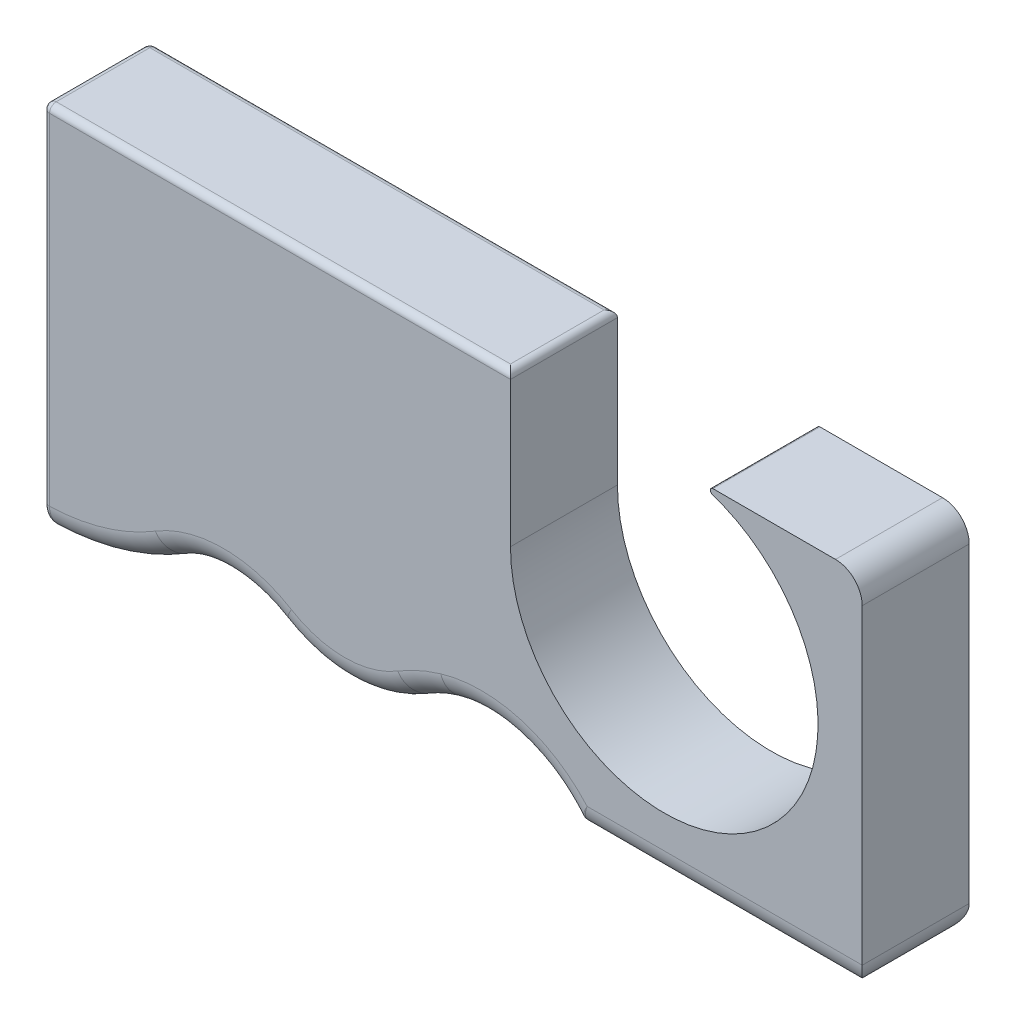
SolidWorks part; units mm, degrees
material "Pure Gold"
ref_plane "Front Plane" through (0, 0, 0) normal (0, 0, 1) x (1, 0, 0)
ref_plane "Top Plane" through (0, 0, 0) normal (0, 1, 0) x (1, 0, 0)
ref_plane "Right Plane" through (0, 0, 0) normal (1, 0, 0) x (0, 0, -1)
sketch "Sketch1" plane through (0, 0, 0) normal (0, 0, 1) x (1, 0, 0)
  line L0 (0, 0) -> (0, 177.546)
  line L1 (0, 177.546) -> (222.9415, 177.546)
  line L3 (389.137, 177.546) -> (222.9415, 177.546)
  line L4 (252.4172, 4.2874) -> (389.137, 4.2874)
  line L5 (389.137, 177.546) -> (389.137, 4.2874)
  arc A0 (0, 0) -> (60.0553, 16.8316) centre (0, 115.5548) ccw
  arc A1 (60.0553, 16.8316) -> (111.4708, 16.8316) centre (85.763, -25.4287) cw
  arc A2 (111.4708, 16.8316) -> (175.1616, 16.8316) centre (143.3162, 69.1813) ccw
  arc A3 (175.1616, 16.8316) -> (192.6023, 24.5751) centre (213.8069, -46.6965) cw
  arc A8 (192.6023, 24.5751) -> (252.4172, 4.2874) centre (208.1854, -27.8017) cw
  dimension "D1" = 177.546
extrude "Boss-Extrude1" add sketch "Sketch1" along normal blind 50.8
sketch "Sketch2" plane through (0, 0, 50.8) normal (0, 0, 1) x (1, 0, 0)
  line L0 (222.0744, 177.546) -> (222.0744, 105.5682)
  line L1 (389.137, 177.546) -> (0, 177.546) construction
  line L2 (222.0744, 177.546) -> (239.7169, 177.546)
  arc A1 (222.0744, 105.5682) -> (322.9091, 173.1035) centre (295.108, 105.5682) ccw
  arc A3 (322.9091, 173.1035) -> (239.7169, 177.546) centre (274.9764, 56.6636) ccw
  dimension "D1" = 73.0337
  dimension "D2" = 125.9198
  dimension "D3" = 222.0744
  dimension "D4" = 239.7169
  dimension "D5" = 274.9764
extrude "Cut-Extrude1" cut sketch "Sketch2" against normal through all
fillet "Fillet1" radius 2.54 1 edges at (252.4172, 4.2874, 25.4)
fillet "Fillet2" radius 12.7 15 edges at (31.1847, 4.2874, 0) (85.763, 24.0366, 0) (143.3162, 7.9063, 0) (183.6325, 21.2652, 0) (225.1456, 24.1456, 0) (31.1847, 4.2874, 50.8) (85.763, 24.0366, 50.8) (143.3162, 7.9063, 50.8) (183.6325, 21.2652, 50.8) (225.1456, 24.1456, 50.8) (389.137, 4.2874, 25.4) (321.4155, 4.2874, 0) (321.4155, 4.2874, 50.8) (252.5661, 4.5516, 0) (252.5661, 4.5516, 50.8)
fillet "Fillet8" radius 1.27 1 edges at (310.2359, 177.546, 25.4)
fillet "Fillet11" radius 12.7 1 edges at (389.137, 177.546, 25.4)
fillet "Fillet12" radius 3.175 4 edges at (111.0372, 177.546, 0) (0, 177.546, 25.4) (111.0372, 177.546, 50.8) (222.0744, 177.546, 25.4)
fillet "Fillet13" radius 3.175 7 edges at (0.9299, 176.6161, 49.8701) (0, 93.5355, 50.8) (0, 3.7197, 47.0803) (0, 0, 25.4) (0, 3.7197, 3.7197) (0, 93.5355, 0) (0.9299, 176.6161, 0.9299)
sketch "Sketch3" plane through (0, 0, 0) normal (-1, 0, 0) x (0, 0, 1)
  line L0 (25.4, 177.546) -> (25.4, 0) construction
  line L1 (3.175, 177.546) -> (47.625, 177.546) construction
  line L2 (25.4, 88.773) -> (50.8, 88.773) construction
  line L5 (50.8, 174.371) -> (50.8, 12.749) construction
  line L6 (25.4, 88.773) -> (0, 88.773) construction
  line L7 (0, 12.749) -> (0, 174.371) construction
  circle A0 centre (25.1453, 139.573) radius 6.35
  circle A2 centre (25.4, 37.973) radius 6.35
  point P9 (25.4, 88.773)
  dimension "D1" = 12.7
  dimension "D2" = 12.7
  dimension "D4" = 50.8
  dimension "D3" = 50.8
sketch "Sketch4" plane through (0, 0, 0) normal (-1, 0, 0) x (0, 0, 1)
  circle A0 centre (25.4, 88.773) radius 6.35
  dimension "D1" = 12.7
extrude "Cut-Extrude2" cut sketch "Sketch4" against normal blind 12.7
extrude "Boss-Extrude2" add sketch "Sketch3" along normal blind 2.54 separate body
